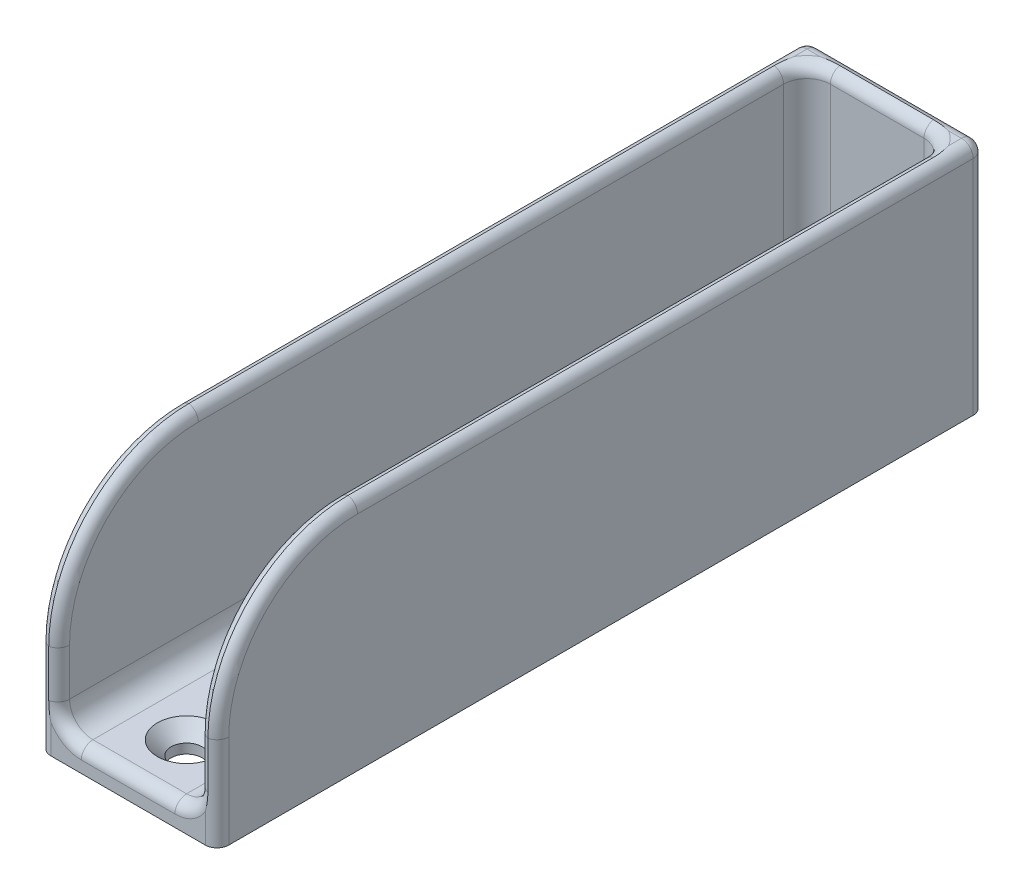
SolidWorks part; units mm, degrees
ref_plane "Front Plane" through (0, 0, 0) normal (0, 0, 1) x (1, 0, 0)
ref_plane "Top Plane" through (0, 0, 0) normal (0, 1, 0) x (1, 0, 0)
ref_plane "Right Plane" through (0, 0, 0) normal (1, 0, 0) x (0, 0, -1)
sketch "Sketch1" plane through (0, 0, 0) normal (0, 1, 0) x (1, 0, 0)
  line L1 (-9.525, -50.8) -> (9.525, -50.8)
  line L2 (-9.525, -50.8) -> (-9.525, 50.8)
  line L3 (-9.525, 50.8) -> (9.525, 50.8)
  line L4 (9.525, -50.8) -> (9.525, 50.8)
  line L5 (-9.525, -50.8) -> (9.525, 50.8) construction
  line L6 (-9.525, 50.8) -> (9.525, -50.8) construction
  point P0 (0, 0)
  dimension "D1" = 19.05
  dimension "D2" = 101.6
extrude "Boss-Extrude1" add sketch "Sketch1" along normal blind 3.175
sketch "Sketch2" plane through (0, 0, 0) normal (0, 1, 0) x (1, 0, 0)
  line L0 (-12.065, 53.34) -> (-12.065, -50.8)
  line L1 (-12.065, -53.34) -> (12.065, -53.34) construction
  line L2 (12.065, -50.8) -> (12.065, 53.34)
  line L3 (12.065, 53.34) -> (-12.065, 53.34)
  line L4 (9.525, -50.8) -> (9.525, 50.8)
  line L5 (9.525, 50.8) -> (-9.525, 50.8)
  line L6 (-9.525, 50.8) -> (-9.525, -50.8)
  line L7 (-9.525, -50.8) -> (9.525, -50.8)
  line L8 (9.525, -50.8) -> (9.525, 50.8)
  line L9 (9.525, 50.8) -> (-9.525, 50.8)
  line L10 (-9.525, 50.8) -> (-9.525, -50.8)
  line L11 (-9.525, -50.8) -> (9.525, -50.8) construction
  line L12 (-9.525, -50.8) -> (-12.065, -50.8)
  line L13 (9.525, -50.8) -> (12.065, -50.8)
  line L14 (-12.065, -50.8) -> (-12.065, -53.34) construction
  line L15 (-12.065, 53.34) -> (-12.065, -53.34) construction
  line L16 (12.065, -53.34) -> (12.065, -50.8) construction
  line L17 (12.065, -53.34) -> (12.065, 53.34) construction
  dimension "D1" = 0
  dimension "D2" = 2.54
extrude "Boss-Extrude2" add sketch "Sketch2" along normal blind 31.75
fillet "Fillet1" radius 19.05 2 edges at (10.795, 31.75, 50.8) (-10.795, 31.75, 50.8)
fillet "Fillet2" radius 3.175 5 edges at (-9.525, 17.4625, -50.8) (-9.525, 3.175, 0) (9.525, 3.175, 0) (9.525, 17.4625, -50.8) (0, 3.175, -50.8)
fillet "Fillet3" radius 1.5875 21 edges at (12.065, 26.1704, 45.2204) (-12.065, 26.1704, 45.2204) (-9.525, 26.1704, 45.2204) (9.525, 26.1704, 45.2204) (9.525, 9.525, 50.8) (8.5951, 4.1049, 50.8) (0, 3.175, 50.8) (-8.5951, 4.1049, 50.8) (-8.5951, 31.75, -49.8701) (-9.525, 31.75, -7.9375) (-12.065, 31.75, -10.795) (0, 31.75, -53.34) (12.065, 31.75, -10.795) (9.525, 31.75, -7.9375) (8.5951, 31.75, -49.8701) (0, 31.75, -50.8) (-12.065, 15.875, -53.34) (12.065, 15.875, -53.34) (12.065, 6.35, 50.8) (-12.065, 6.35, 50.8) (-9.525, 9.525, 50.8)
sketch "Sketch3" plane through (0, 3.175, 0) normal (0, 1, 0) x (1, 0, 0)
  line L0 (-6.35, 47.625) -> (0, 41.275) construction
  line L1 (0, 41.275) -> (6.35, 47.625) construction
  line L2 (-6.35, -49.2125) -> (0, -42.8625) construction
  line L3 (0, -42.8625) -> (6.35, -49.2125) construction
  circle A0 centre (0, 41.275) radius 2.0955
  circle A1 centre (0, -42.8625) radius 2.0955
  dimension "D1" = 4.191
extrude "Cut-Extrude1" cut sketch "Sketch3" against normal through all
sketch "Sketch4" plane through (0, 3.175, 0) normal (0, 1, 0) x (1, 0, 0)
  circle A0 centre (0, 41.275) radius 3.9688
  circle A1 centre (0, -42.8625) radius 3.9688
  dimension "D1" = 7.9375
extrude "Cut-Extrude2" cut sketch "Sketch4" against normal through all draft 45
